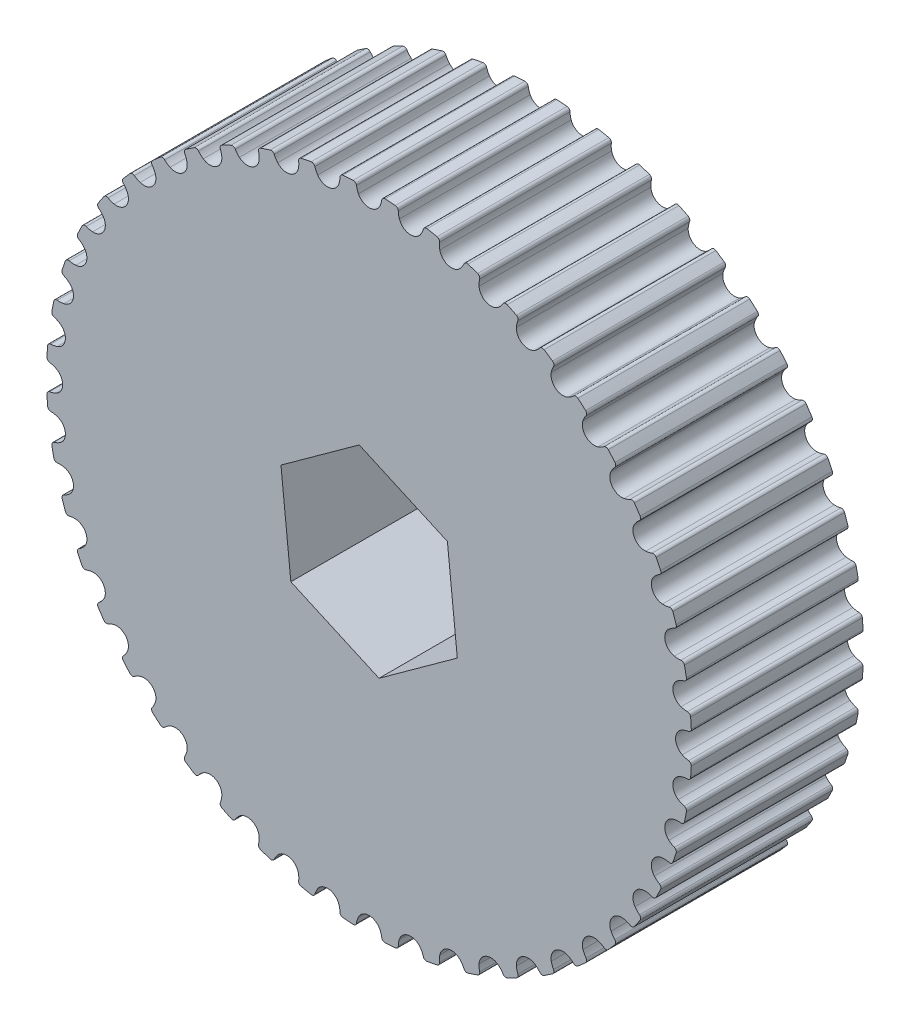
SolidWorks part; units mm, degrees
ref_plane "Front Plane" through (0, 0, 0) normal (0, 0, 1) x (1, 0, 0)
ref_plane "Top Plane" through (0, 0, 0) normal (0, 1, 0) x (1, 0, 0)
ref_plane "Right Plane" through (0, 0, 0) normal (1, 0, 0) x (0, 0, -1)
sketch "Sketch1" plane through (0, 0, 0) normal (0, 0, 1) x (1, 0, 0)
  line L1 (-1.7022, 14.274) -> (1.8807, 14.274) construction
  line L4 (0, 0) -> (0, 14.274) construction
  line L6 (0, 15.278) -> (1.9957, 15.1471) construction
  line L7 (1.9957, 15.1471) -> (2.8688, 15.0321) construction
  line L8 (1.9957, 15.1471) -> (1.8807, 14.274) construction
  line L9 (-1.7434, 14.3321) -> (-1.7022, 14.274) construction
  line L10 (-2.1266, 14.8727) -> (-2.4139, 15.278)
  line L11 (-2.4139, 15.278) -> (2.013, 15.278)
  line L12 (2.013, 15.278) -> (1.9625, 14.8953)
  circle A0 centre (0, 0) radius 15.278 construction
  circle A2 centre (0, 0) radius 15.024 construction
  arc A3 (-0.4989, 14.5858) -> (0.4989, 14.5858) centre (0, 14.829) ccw
  arc A4 (-0.4989, 14.5858) -> (-0.5892, 14.8777) centre (0.4, 15.024) cw
  arc A5 (-2.1266, 14.8727) -> (-0.7451, 15.0055) centre (0, 0) cw
  arc A6 (-0.5892, 14.8777) -> (-0.7451, 15.0055) centre (-0.7376, 14.8557) ccw
  arc A7 (1.9625, 14.8953) -> (0.7451, 15.0055) centre (0, 0) ccw
  arc A8 (0.5892, 14.8777) -> (0.7451, 15.0055) centre (0.7376, 14.8557) cw
  arc A9 (0.4989, 14.5858) -> (0.5892, 14.8777) centre (-0.4, 15.024) ccw
  point P11 (0, 15.278)
  point P14 (0, 15.024)
  dimension "PD" = 30.556
  dimension "R3" = 0.555
  dimension "R2" = 1
  dimension "R1" = 0.15
  dimension "b" = 0.4
  dimension "D3" = 2
  dimension "PLD" = 0.254
  dimension "h" = 0.75
sketch "Sketch2" plane through (0, 0, 0) normal (1, 0, 0) x (0, 0, -1)
  line L1 (-4, 0) -> (-4, 15.024)
  line L6 (-4, 15.024) -> (4, 15.024)
  line L9 (4, 15.024) -> (4, 0)
  line L10 (-4, 0) -> (4, 0)
  dimension "Inside Width" = 8
revolve "Revolve1" add sketch "Sketch2" angle 360 mid plane about L10
sketch "Sketch3" plane through (0, 0, 0) normal (0, 0, 1) x (1, 0, 0)
  line L6 (2.013, 15.278) -> (-2.4139, 15.278)
  line L7 (1.9625, 14.8953) -> (2.013, 15.278)
  line L8 (-2.4139, 15.278) -> (-2.1266, 14.8727)
  line L9 (2.013, 15.278) -> (-2.4139, 15.278)
  line L10 (1.9625, 14.8953) -> (2.013, 15.278)
  line L11 (-2.4139, 15.278) -> (-2.1266, 14.8727)
  arc A8 (1.9625, 14.8953) -> (0.7451, 15.0055) centre (0, 0) ccw
  arc A9 (0.7451, 15.0055) -> (0.5892, 14.8777) centre (0.7376, 14.8557) ccw
  arc A10 (0.4989, 14.5858) -> (0.5892, 14.8777) centre (-0.4, 15.024) ccw
  arc A11 (-0.4989, 14.5858) -> (0.4989, 14.5858) centre (0, 14.829) ccw
  arc A12 (-0.5892, 14.8777) -> (-0.4989, 14.5858) centre (0.4, 15.024) ccw
  arc A13 (-0.5892, 14.8777) -> (-0.7451, 15.0055) centre (-0.7376, 14.8557) ccw
  arc A14 (-0.7451, 15.0055) -> (-2.1266, 14.8727) centre (0, 0) ccw
  arc A15 (1.9625, 14.8953) -> (0.7451, 15.0055) centre (0, 0) ccw
  arc A16 (0.7451, 15.0055) -> (0.5892, 14.8777) centre (0.7376, 14.8557) ccw
  arc A17 (0.4989, 14.5858) -> (0.5892, 14.8777) centre (-0.4, 15.024) ccw
  arc A18 (-0.4989, 14.5858) -> (0.4989, 14.5858) centre (0, 14.829) ccw
  arc A19 (-0.5892, 14.8777) -> (-0.4989, 14.5858) centre (0.4, 15.024) ccw
  arc A20 (-0.5892, 14.8777) -> (-0.7451, 15.0055) centre (-0.7376, 14.8557) ccw
  arc A21 (-0.7451, 15.0055) -> (-2.1266, 14.8727) centre (0, 0) ccw
  dimension "D1" = 0
extrude "Cut-Extrude1" cut sketch "Sketch3" against normal up to next from surface starting at face at (15.024, 0, 4)
pattern_circular "CirPattern1" count 48 over 360 about axis through (0, 0, 4) along (0, 0, 1) of "Cut-Extrude1"
sketch "Sketch4" plane through (0, 0, 4) normal (0, 0, 1) x (1, 0, 0)
  line L1 (0.461, -4.4763) -> (4.1071, -1.8389)
  line L2 (4.1071, -1.8389) -> (3.6461, 2.6374)
  line L3 (3.6461, 2.6374) -> (-0.461, 4.4763)
  line L4 (-0.461, 4.4763) -> (-4.1071, 1.8389)
  line L5 (-4.1071, 1.8389) -> (-3.6461, -2.6374)
  line L6 (-3.6461, -2.6374) -> (0.461, -4.4763)
  circle A0 centre (0, 0) radius 3.8971 construction
  circle A1 centre (0, 0) radius 4.5 construction
  dimension "D1" = 9
extrude "Cut-Extrude2" cut sketch "Sketch4" against normal up to next
ref_axis "Center Axis 1" through (0, 0, -7.135) along (0, 0, 1)
ref_plane "Contact Plane 1" through (0, 0, 7.135) normal (0, 0, 1) x (1, 0, 0)
ref_plane "Contact Plane 2" through (0, 0, -7.135) normal (0, 0, -1) x (-1, 0, 0)
